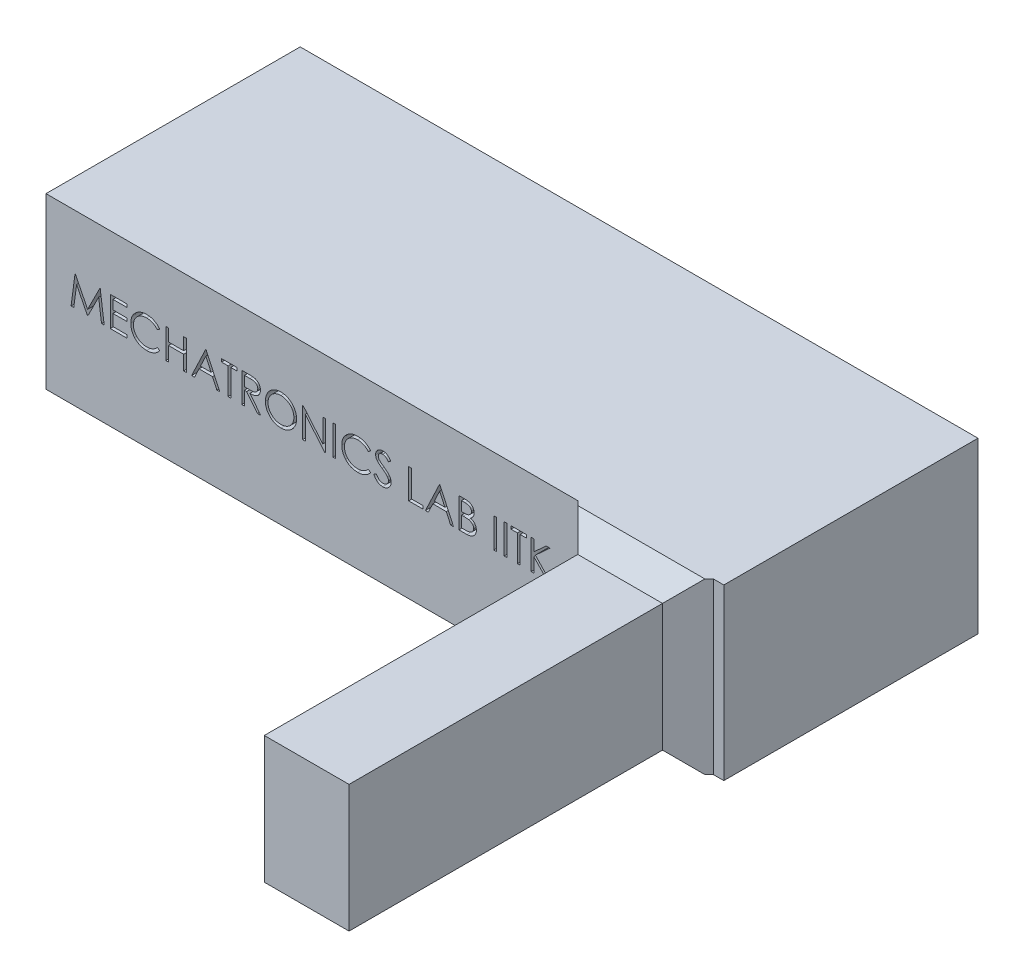
SolidWorks part; units mm, degrees
ref_plane "Front Plane" through (0, 0, 0) normal (0, 0, 1) x (1, 0, 0)
ref_plane "Top Plane" through (0, 0, 0) normal (0, 1, 0) x (1, 0, 0)
ref_plane "Right Plane" through (0, 0, 0) normal (1, 0, 0) x (0, 0, -1)
sketch "Sketch1" plane through (0, 0, 0) normal (1, 0, 0) x (0, 0, -1)
  line L1 (-15, 10) -> (15, 10)
  line L2 (-15, 10) -> (-15, -10)
  line L3 (-15, -10) -> (15, -10)
  line L4 (15, 10) -> (15, -10)
  line L5 (-15, 10) -> (15, -10) construction
  line L6 (-15, -10) -> (15, 10) construction
  point P0 (0, 0)
  dimension "D1" = 30
  dimension "D2" = 20
extrude "Boss-Extrude1" add sketch "Sketch1" along normal blind 80
sketch "Sketch2" plane through (0, 0, 15) normal (0, 0, 1) x (1, 0, 0)
  line L0 (0, 0) -> (80, 0) construction
  line L1 (80, 10) -> (80, -10) construction
  line L3 (65.7663, 7.5) -> (75.7663, 7.5)
  line L4 (65.7663, 7.5) -> (65.7663, -7.5)
  line L5 (65.7663, -7.5) -> (75.7663, -7.5)
  line L6 (75.7663, 7.5) -> (75.7663, -7.5)
  line L7 (65.7663, 7.5) -> (75.7663, -7.5) construction
  line L8 (65.7663, -7.5) -> (75.7663, 7.5) construction
  point P5 (70.7663, 0)
  dimension "D1" = 10
  dimension "D2" = 15
extrude "Boss-Extrude2" add sketch "Sketch2" along normal blind 40
chamfer "Chamfer1" distance 3 angle 45 4 edges at (65.7663, 0, 15) (70.7663, -7.5, 15) (75.7663, 0, 15) (70.7663, 7.5, 15)
sketch "Sketch3" plane through (0, 0, 15) normal (0, 0, 1) x (1, 0, 0)
  line L0 (0, 0) -> (62.7663, 0) construction
  line L1 (62.7663, -10) -> (62.7663, 10) construction
  text T0 "  MECHATRONICS LAB IITK"
extrude "Cut-Extrude1" cut sketch "Sketch3" against normal blind 2
